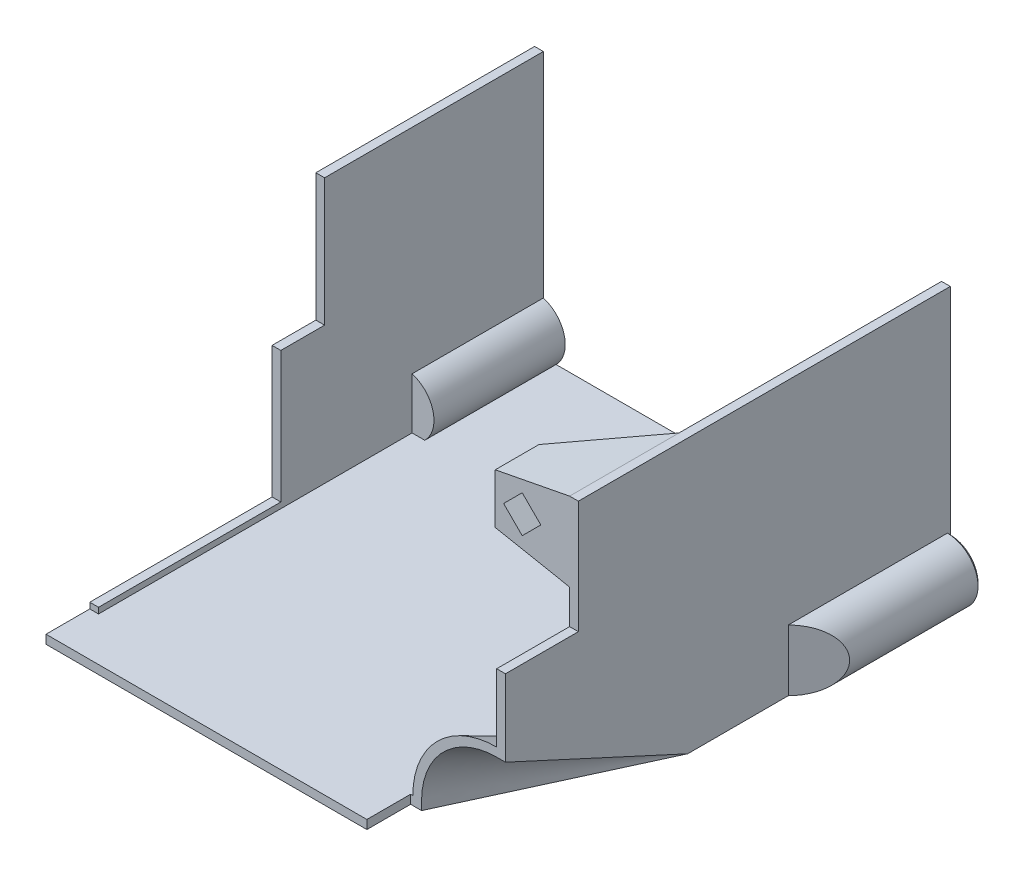
SolidWorks part; units mm, degrees
material "Custom Plastic"
ref_plane "Front Plane" through (0, 0, 0) normal (0, 0, 1) x (1, 0, 0)
ref_plane "Top Plane" through (0, 0, 0) normal (0, 1, 0) x (1, 0, 0)
ref_plane "Right Plane" through (0, 0, 0) normal (1, 0, 0) x (0, 0, -1)
sketch "Sketch1" plane through (0, 0, 0) normal (0, 0, 1) x (1, 0, 0)
  line L1 (-33.6475, 16.5475) -> (-34.8475, 16.5475)
  line L2 (-33.6475, -19.7525) -> (-33.6475, -20.9525) construction
  line L3 (-31.9081, -19.7525) -> (19.2131, -19.7525)
  line L4 (20.9525, 16.5475) -> (20.9525, -12.7276)
  line L5 (-33.6475, -12.7276) -> (-33.6475, 16.5475)
  line L7 (20.9525, 16.5475) -> (22.1525, 16.5475)
  line L8 (-34.8475, 16.5475) -> (-34.8475, -12.5525)
  line L9 (-34.8475, -20.9525) -> (22.1525, -20.9525)
  line L10 (22.1525, 16.5475) -> (22.1525, -12.5525)
  arc A0 (22.1525, -20.9525) -> (22.1525, -12.5525) centre (22.1525, -16.7525) ccw
  circle A1 centre (22.1525, -16.7525) radius 1.6 construction
  arc A2 (20.9525, -12.7276) -> (19.2131, -19.7525) centre (22.1525, -16.7525) ccw
  circle A3 centre (-34.8475, -16.7525) radius 1.6 construction
  arc A4 (-34.8475, -12.5525) -> (-34.8475, -20.9525) centre (-34.8475, -16.7525) ccw
  arc A6 (-31.9081, -19.7525) -> (-33.6475, -12.7276) centre (-34.8475, -16.7525) ccw
  dimension "D2" = 3.2
  dimension "D5" = 4.2
  dimension "D1" = 1.2
  dimension "D3" = 57
  dimension "D4" = 37.5
extrude "Boss-Extrude1" add sketch "Sketch1" along normal blind 67
sketch "Sketch2" plane through (0, 0, 67) normal (0, 0, 1) x (1, 0, 0)
  line L0 (-34.8475, -20.9525) -> (22.1525, -20.9525) construction
  line L1 (9.1525, -20.9525) -> (32.8781, -20.9525)
  line L2 (9.1525, -20.9525) -> (9.1525, -19.7525)
  line L3 (-34.8475, 12.6741) -> (32.8781, 12.6741)
  line L4 (32.8781, -20.9525) -> (32.8781, 12.6741)
  line L5 (22.1525, -12.5525) -> (22.1525, 16.5475) construction
  line L6 (9.1525, -19.7525) -> (-34.8475, -19.7525)
  line L7 (19.2131, -19.7525) -> (-31.9081, -19.7525) construction
  line L8 (-34.8475, 16.5475) -> (-34.8475, -12.5525) construction
  line L9 (-34.8475, -20.9525) -> (-34.8475, -19.7525)
  line L10 (-34.8475, -20.9525) -> (-42.7406, -20.9525)
  line L11 (-34.8475, -20.9525) -> (22.1525, -20.9525) construction
  line L12 (-42.7406, -20.9525) -> (-42.7406, -7.5075)
  line L13 (-42.7406, -7.5075) -> (-34.8475, -7.5075)
  line L14 (-34.8475, -7.5075) -> (-34.8475, 12.6741)
  dimension "D1" = 13
extrude "Cut-Extrude1" cut sketch "Sketch2" against normal blind 6
sketch "Sketch3" plane through (0, 0, 61) normal (0, 0, 1) x (1, 0, 0)
  line L0 (22.1525, -12.5525) -> (22.1525, 12.6741) construction
  line L1 (-34.8475, 16.5475) -> (22.1525, 16.5475)
  line L2 (-34.8475, 16.5475) -> (-34.8475, 1.0475)
  line L3 (-34.8475, 1.0475) -> (22.1525, 1.0475)
  line L4 (22.1525, 16.5475) -> (22.1525, 1.0475)
  dimension "D1" = 15.5
extrude "Cut-Extrude2" cut sketch "Sketch3" against normal blind 10 and the other way blind 10
sketch "Sketch4" plane through (0, 0, 51) normal (0, 0, 1) x (1, 0, 0)
  line L0 (-34.8475, 16.5475) -> (-34.8475, 1.0475) construction
  line L1 (-34.8475, 16.5475) -> (-33.6475, 16.5475)
  line L2 (-34.8475, 16.5475) -> (-34.8475, -0.9525)
  line L3 (-34.8475, -0.9525) -> (-33.6475, -0.9525)
  line L4 (-33.6475, 16.5475) -> (-33.6475, -0.9525)
extrude "Cut-Extrude3" cut sketch "Sketch4" against normal blind 21
sketch "Sketch6" plane through (0, 0, 0) normal (0, 0, -1) x (-1, 0, 0)
  circle A0 centre (-22.1525, -16.7525) radius 1.65
  circle A1 centre (34.8475, -16.7525) radius 1.65
  arc A2 (34.8475, -20.9525) -> (34.8475, -12.5525) centre (34.8475, -16.7525) ccw construction
  arc A3 (-22.1525, -12.5525) -> (-22.1525, -20.9525) centre (-22.1525, -16.7525) ccw construction
  dimension "D1" = 3.3
extrude "Cut-Extrude4" cut sketch "Sketch6" against normal blind 16
sketch "Sketch7" plane through (0, 0, 61) normal (0, 0, 1) x (1, 0, 0)
  line L0 (19.2131, -19.7525) -> (9.1525, -19.7525) construction
  line L1 (22.1525, -12.5525) -> (31.8181, -12.5525)
  line L2 (22.1525, -12.5525) -> (22.1525, -20.9525)
  line L3 (22.1525, -20.9525) -> (31.8181, -20.9525)
  line L4 (31.8181, -12.5525) -> (31.8181, -20.9525)
  line L5 (20.9525, -12.7276) -> (15.0843, -12.7276)
  line L6 (20.9525, -12.7276) -> (20.9525, -19.7525)
  line L7 (20.9525, -19.7525) -> (15.0843, -19.7525)
  line L8 (15.0843, -12.7276) -> (15.0843, -19.7525)
  line L9 (-33.6475, -12.7276) -> (-33.6475, 1.0475) construction
  line L10 (-34.8475, -20.9525) -> (-44.0251, -20.9525)
  line L11 (-34.8475, -20.9525) -> (-34.8475, -7.6032)
  line L12 (-34.8475, -7.6032) -> (-44.0251, -7.6032)
  line L13 (-44.0251, -20.9525) -> (-44.0251, -7.6032)
  line L14 (-33.6475, -7.6032) -> (-26.816, -7.6032)
  line L15 (-33.6475, -7.6032) -> (-33.6475, -19.7525)
  line L16 (-33.6475, -19.7525) -> (-26.816, -19.7525)
  line L17 (-26.816, -7.6032) -> (-26.816, -19.7525)
  line L18 (9.1525, -19.7525) -> (-34.8475, -19.7525) construction
extrude "Cut-Extrude5" cut sketch "Sketch7" against normal offset from surface (43 mm away) 18 up to face at (-36.4975, -16.7525, 0)
chamfer "Chamfer1" distance 4.2 angle 45 2 edges at (22.1525, -16.7525, 18) (-34.8475, -16.7525, 18)
chamfer "Chamfer3" distance 0.6 angle 30 2 edges at (20.5025, -16.7525, 0) (-36.4975, -16.7525, 0) first distance on face at (20.5025, -16.7525, 16) first distance on face at (-36.4975, -16.7525, 16)
chamfer "Chamfer4" distance 0.4 angle 45 3 edges at (-39.0475, -16.7525, 0) (-6.3475, -20.9525, 0) (26.3525, -16.7525, 0)
sketch "Sketch8" plane through (0, 0, 51) normal (0, 0, 1) x (1, 0, 0)
  line L0 (14.4525, 12.7475) -> (10.7525, 12.7475) construction
  line L1 (11.9025, 11.1475) -> (14.4525, 13.6975)
  line L2 (10.7525, 9.5475) -> (14.4525, 9.5475) construction
  line L4 (10.7525, 14.5725) -> (10.7525, 12.7475)
  line L5 (10.7525, 9.5475) -> (10.7525, 7.7225)
  line L7 (20.9525, 16.5475) -> (20.9525, 1.0475) construction
  line L8 (20.9525, 5.7475) -> (22.1525, 5.7475)
  line L9 (22.1525, 1.0475) -> (22.1525, 16.5475) construction
  line L10 (22.1525, 5.7475) -> (22.1525, 16.5475)
  line L11 (22.1525, 16.5475) -> (20.9525, 16.5475)
  line L12 (11.9025, 11.1475) -> (14.4525, 8.5975)
  line L13 (14.4525, 13.6975) -> (17.0025, 11.1475)
  line L14 (14.4525, 8.5975) -> (17.0025, 11.1475)
  line L15 (11.9025, 11.1475) -> (22.1525, 11.1475) construction
  line L16 (14.4525, 13.6975) -> (14.4525, 8.5975) construction
  line L17 (10.7525, 12.7475) -> (10.7525, 9.5475)
  line L18 (20.9525, 16.5475) -> (10.7525, 14.5725)
  line L19 (20.9525, 5.7475) -> (10.7525, 7.7225)
  arc A0 (14.4525, 9.5475) -> (14.4525, 12.7475) centre (14.4525, 11.1475) ccw construction
  circle A1 centre (14.4525, 11.1475) radius 2.55 construction
  dimension "D1" = 1.6
  dimension "D5" = 5.1
  dimension "D2" = 6.5
  dimension "D3" = 5.4
  dimension "D4" = 10.2
  dimension "D6" = 6.85
extrude "Boss-Extrude2" add sketch "Sketch8" against normal blind 15
sketch "Sketch10" plane through (0, 0, 36) normal (0, 0, -1) x (-1, 0, 0)
  line L0 (-14.4525, 14.1475) -> (-10.7525, 14.1475)
  line L1 (-10.7525, 14.5725) -> (-10.7525, 7.7225) construction
  line L2 (-10.7525, 14.1475) -> (-10.7525, 8.1475)
  line L3 (-10.7525, 8.1475) -> (-14.4525, 8.1475)
  line L5 (-14.4525, 13.6975) -> (-14.4525, 8.5975) construction
  arc A0 (-14.4525, 14.1475) -> (-14.4525, 8.1475) centre (-14.4525, 11.1475) ccw
  arc A1 (-14.4525, 8.1475) -> (-14.4525, 14.1475) centre (-14.4525, 11.1475) ccw construction
  dimension "D1" = 3
extrude "Cut-Extrude6" cut sketch "Sketch10" against normal offset from surface 6 and the other way blind 10 up to face at (18.3811, 9.0332, 51)
sketch "Sketch11" plane through (0, 16.5475, 0) normal (0, 1, 0) x (1, 0, 0)
  line L0 (20.9525, -36) -> (10.7525, -45)
  line L1 (10.7525, -36) -> (10.7525, -51) construction
  line L2 (10.7525, -45) -> (10.7525, -36)
  line L3 (10.7525, -36) -> (20.9525, -36)
extrude "Cut-Extrude7" cut sketch "Sketch11" against normal up to surface and the other way blind 10 up to face at (15.8525, 6.735, 43.5)
sketch "Sketch12" plane through (0, 1.0475, 0) normal (0, 1, 0) x (1, 0, 0)
  line L0 (-34.8475, -61) -> (-34.8475, -51) construction
  line L1 (-34.8475, -36) -> (-33.6475, -36)
  line L2 (-34.8475, -36) -> (-34.8475, -61)
  line L3 (-34.8475, -61) -> (-33.6475, -61)
  line L4 (-33.6475, -36) -> (-33.6475, -61)
  line L5 (-33.6475, -30) -> (-34.8475, -30) construction
  point P7 (-34.2475, -30)
  dimension "D1" = 6
extrude "Cut-Extrude8" cut sketch "Sketch12" against normal offset from surface (20 mm away) 0.8 up to face at (-8.5141, -19.7525, 37.5)
sketch "Sketch13" plane through (0, 0, 61) normal (0, 0, 1) x (1, 0, 0)
  line L0 (20.9525, 1.0475) -> (20.9525, -19.7525) construction
  line L1 (20.9525, -19.7525) -> (9.1525, -19.7525) construction
  line L2 (9.4525, -19.7525) -> (20.9525, -19.7525)
  line L3 (20.9525, -19.7525) -> (20.9525, -8.2525)
  arc A0 (20.9525, -8.2525) -> (9.4525, -19.7525) centre (20.9525, -19.7525) ccw
  dimension "D1" = 11.5
sketch "Sketch14" plane through (20.9525, 0, 0) normal (-1, 0, 0) x (0, 0, 1)
  line L0 (18, -19.7525) -> (61, -19.7525) construction
  line L1 (61, 1.0475) -> (61, -19.7525) construction
  point P0 (36, -19.7525)
  dimension "D1" = 25
loft "Loft1" add profiles "Sketch13", "Sketch14"
sketch "Sketch15" plane through (0, 0, 61) normal (0, 0, 1) x (1, 0, 0)
  line L2 (20.9525, -9.4525) -> (22.1525, -9.4525)
  line L4 (22.1525, -20.9525) -> (22.1525, -12.5525) construction
  line L5 (22.1525, -9.4525) -> (22.1525, -20.9525)
  line L6 (22.1525, -20.9525) -> (10.6525, -20.9525)
  line L7 (9.1525, -20.9525) -> (22.1525, -20.9525) construction
  line L8 (10.6525, -20.9525) -> (10.6525, -19.7525)
  line L9 (20.9525, -9.4525) -> (20.9525, -8.2525) construction
  line L10 (20.9525, -8.2525) -> (22.1525, -8.2525) construction
  line L11 (22.1525, -20.9525) -> (22.1525, 1.0475) construction
  arc A0 (20.9525, -9.4525) -> (10.6525, -19.7525) centre (20.9525, -19.7525) ccw
  arc A1 (22.1525, -20.9525) -> (26.3525, -16.7525) centre (22.1525, -16.7525) ccw construction
sketch "Sketch16" plane through (22.1525, 0, 0) normal (1, 0, 0) x (0, 0, -1)
  line L0 (-61, -20.9525) -> (-22.2, -20.9525) construction
  point P0 (-36, -20.9525)
loft "Cut-Loft1" cut profiles "Sketch15", "Sketch16"
equation "\"y-cross-rib-thickness\"=6"
equation "\"y-rib-thickness\"=6"
equation "\"bed-plate-thickness\"=6"
equation "\"x-plate-thickness\"=5"
equation "\"rod-diameter\"=12"
equation "\"t-nut-hole-diameter\"=3"
equation "\"y-plate-thickness\"=5"
equation "\"enclosure-thickness\"=0.6"
equation "\"M3-Clearance\"=3.3"
equation "\"M4-Clearance\"=4.3"
equation "\"M5-Clearance\"=5.3"
equation "\"M6-Clearance\"=6.3"
equation "\"M8-Clearance\"=8.3"
equation "\"623-Bearing-Dia\"=11.2"
